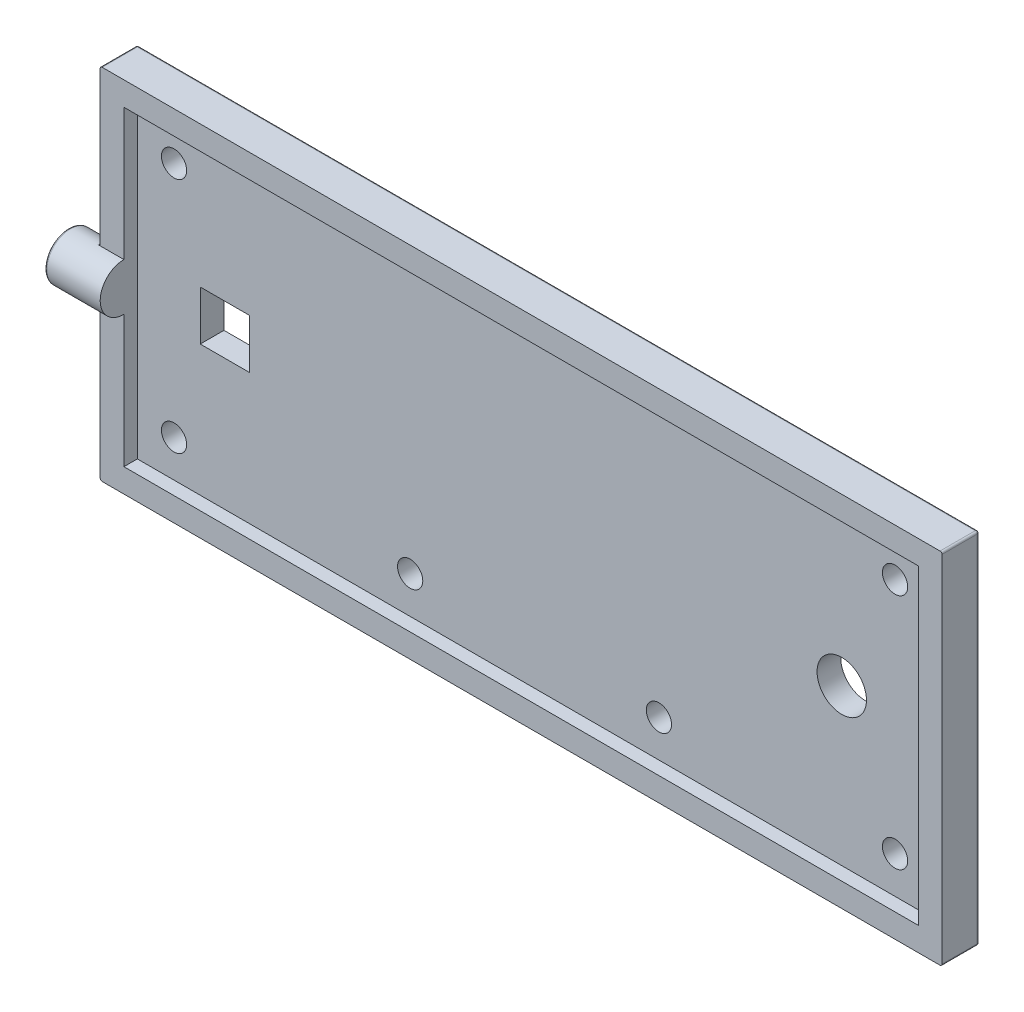
SolidWorks part; units mm, degrees
ref_plane "Front Plane" through (0, 0, 0) normal (0, 0, 1) x (1, 0, 0)
ref_plane "Top Plane" through (0, 0, 0) normal (0, 1, 0) x (1, 0, 0)
ref_plane "Right Plane" through (0, 0, 0) normal (1, 0, 0) x (0, 0, -1)
sketch "Sketch1" plane through (0, 0, 0) normal (0, 0, 1) x (1, 0, 0)
  line L0 (92.08, 42.37) -> (92.08, 3) construction
  line L1 (0, 0) -> (106.46, 0)
  line L2 (0, 0) -> (0, 45.37)
  line L3 (0, 45.37) -> (106.46, 45.37)
  line L4 (106.46, 0) -> (106.46, 45.37)
  line L5 (3, 3) -> (103.46, 3)
  line L6 (3, 3) -> (3, 42.37)
  line L7 (3, 42.37) -> (103.46, 42.37)
  line L8 (103.46, 3) -> (103.46, 42.37)
  line L10 (10.955, 25.81) -> (17.205, 25.81)
  line L11 (10.955, 25.81) -> (10.955, 19.56)
  line L12 (10.955, 19.56) -> (17.205, 19.56)
  line L13 (17.205, 25.81) -> (17.205, 19.56)
  line L14 (10.955, 25.81) -> (17.205, 19.56) construction
  line L15 (10.955, 19.56) -> (17.205, 25.81) construction
  circle A0 centre (7.64, 7.68) radius 1.595
  circle A1 centre (37.5, 7.68) radius 1.595
  circle A2 centre (68.96, 7.68) radius 1.595
  circle A3 centre (98.82, 7.68) radius 1.595
  circle A4 centre (7.64, 37.69) radius 1.595
  circle A5 centre (98.82, 37.69) radius 1.595
  circle A6 centre (92.08, 22.685) radius 3.125
  point P25 (14.08, 22.685)
  point P30 (0, 0)
  dimension "D7" = 3.19
  dimension "D8" = 3.19
  dimension "D9" = 3.19
  dimension "D10" = 3.19
  dimension "D11" = 3.19
  dimension "D14" = 3.19
  dimension "D19" = 6.25
  dimension "D1" = 45.37
  dimension "D2" = 106.46
  dimension "D3" = 3
  dimension "D4" = 3
  dimension "D5" = 3
  dimension "D6" = 3
  dimension "D12" = 4.68
  dimension "D13" = 4.64
  dimension "D15" = 4.68
  dimension "D16" = 29.86
  dimension "D17" = 31.46
  dimension "D18" = 29.86
  dimension "D20" = 11.38
  dimension "D21" = 78
  dimension "D22" = 6.25
extrude "Boss-Extrude1" add sketch "Sketch1" along normal blind 3 contours L0 L7 L6 L5 A6 A4 A2 A1 A0 | L7 L0 A6 L5 L8 A3 A5 region at (53.3179, 22.7475, 0)
extrude "Boss-Extrude2" add sketch "Sketch1<5>" along normal blind 4.7 contours L1 L4 L3 L2 L8 L5 L6 L7 region at (1.1572, 22.685, 0)
sketch "Sketch1<5>" plane through (0, 0, 0) normal (0, 0, 1) x (1, 0, 0) same geometry as "Sketch1"
sketch "Sketch2" plane through (0, 0, 0) normal (-1, 0, 0) x (0, 0, 1)
  line L0 (4.7, 0) -> (4.7, 45.37) construction
  circle A0 centre (4.7, 22.685) radius 3
extrude "Boss-Extrude3" add sketch "Sketch2" along normal blind 4 and the other way blind 3
fillet "Fillet1" radius 0.25 10 edges at (-4, 22.685, 7.7) (0, 45.37, 2.35) (53.23, 45.37, 0) (106.46, 45.37, 2.35) (106.46, 0, 2.35) (106.46, 22.685, 0) (0, 0, 2.35) (53.23, 0, 0) (0, 22.685, 0) (0, 22.685, 1.7)
